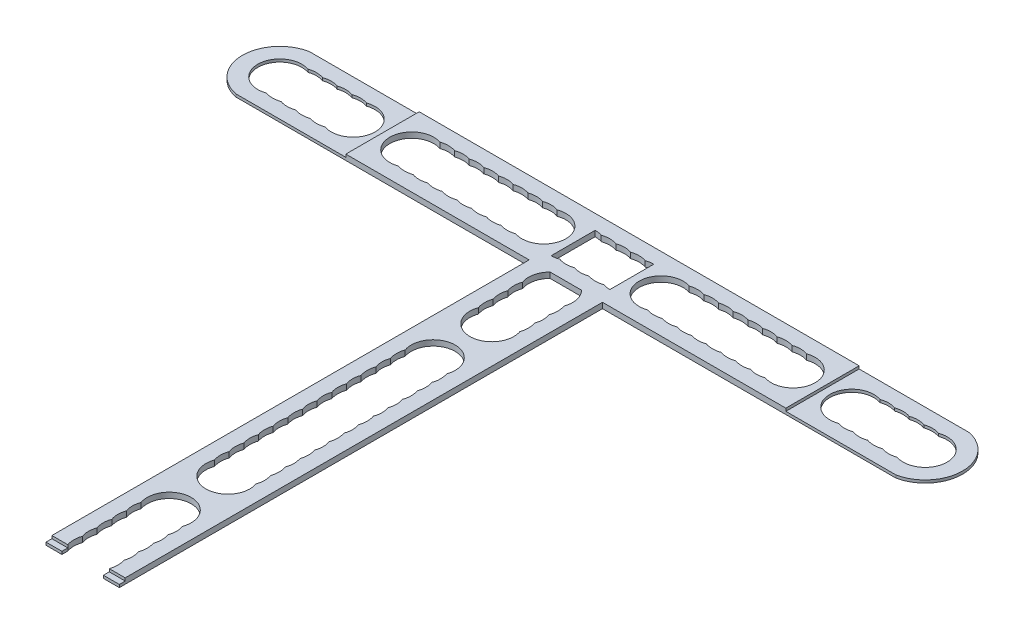
SolidWorks part; units mm, degrees
note: The reader was unsure of these and kept them because the rebuilt part matched: shared geometry of "Sketch3<3>".
ref_plane "Front Plane" through (0, 0, 0) normal (0, 0, 1) x (1, 0, 0)
ref_plane "Top Plane" through (0, 0, 0) normal (0, 1, 0) x (1, 0, 0)
ref_plane "Right Plane" through (0, 0, 0) normal (1, 0, 0) x (0, 0, -1)
sketch "Sketch3" plane through (0, 0, 0) normal (0, 1, 0) x (1, 0, 0)
  line L0 (-112.5, 0) -> (112.5, 0) construction
  line L1 (-112.5, -12.5) -> (112.5, -12.5)
  line L2 (-112.5, -12.5) -> (-112.5, 12.5) construction
  line L3 (-112.5, 12.5) -> (112.5, 12.5)
  line L4 (112.5, -12.5) -> (112.5, 12.5) construction
  line L5 (-112.5, -12.5) -> (112.5, 12.5) construction
  line L6 (-112.5, 12.5) -> (112.5, -12.5) construction
  line L7 (75, 12.5) -> (75, -12.5)
  line L8 (10, 7.5) -> (10, -7.5)
  line L9 (0, 12.5) -> (0, -12.5) construction
  line L10 (0, 12.5) -> (0, -12.5)
  arc A0 (-2.5, 7.0711) -> (2.5, 7.0711) centre (0, 0) cw
  arc A1 (2.5, 7.0711) -> (7.5, 7.0711) centre (5, 0) cw
  arc A2 (7.5, 7.0711) -> (12.5, 7.0711) centre (10, 0) cw
  arc A3 (12.5, 7.0711) -> (17.5, 7.0711) centre (15, 0) cw
  arc A4 (17.5, 7.0711) -> (22.5, 7.0711) centre (20, 0) cw
  arc A5 (22.5, 7.0711) -> (27.5, 7.0711) centre (25, 0) cw
  arc A6 (27.5, 7.0711) -> (32.5, 7.0711) centre (30, 0) cw
  arc A7 (32.5, 7.0711) -> (37.5, 7.0711) centre (35, 0) cw
  arc A8 (37.5, 7.0711) -> (42.5, 7.0711) centre (40, 0) cw
  arc A9 (42.5, 7.0711) -> (47.5, 7.0711) centre (45, 0) cw
  arc A10 (47.5, 7.0711) -> (52.5, 7.0711) centre (50, 0) cw
  arc A11 (52.5, 7.0711) -> (57.5, 7.0711) centre (55, 0) cw
  arc A12 (57.5, 7.0711) -> (62.5, 7.0711) centre (60, 0) cw
  arc A13 (62.5, 7.0711) -> (67.5, 7.0711) centre (65, 0) cw
  arc A14 (67.5, 7.0711) -> (72.5, 7.0711) centre (70, 0) cw
  arc A15 (72.5, 7.0711) -> (77.5, 7.0711) centre (75, 0) cw
  arc A16 (77.5, 7.0711) -> (82.5, 7.0711) centre (80, 0) cw
  arc A17 (82.5, 7.0711) -> (87.5, 7.0711) centre (85, 0) cw
  arc A18 (87.5, 7.0711) -> (92.5, 7.0711) centre (90, 0) cw
  arc A19 (92.5, 7.0711) -> (97.5, 7.0711) centre (95, 0) cw
  arc A20 (97.5, 7.0711) -> (102.5, 7.0711) centre (100, 0) cw
  arc A21 (102.5, 7.0711) -> (107.5, 7.0711) centre (105, 0) cw
  arc A22 (107.5, 7.0711) -> (112.5, 7.0711) centre (110, 0) cw
  arc A23 (107.5, -7.0711) -> (112.5, -7.0711) centre (110, 0) ccw
  arc A24 (102.5, -7.0711) -> (107.5, -7.0711) centre (105, 0) ccw
  arc A25 (97.5, -7.0711) -> (102.5, -7.0711) centre (100, 0) ccw
  arc A26 (92.5, -7.0711) -> (97.5, -7.0711) centre (95, 0) ccw
  arc A27 (87.5, -7.0711) -> (92.5, -7.0711) centre (90, 0) ccw
  arc A28 (82.5, -7.0711) -> (87.5, -7.0711) centre (85, 0) ccw
  arc A29 (77.5, -7.0711) -> (82.5, -7.0711) centre (80, 0) ccw
  arc A30 (72.5, -7.0711) -> (77.5, -7.0711) centre (75, 0) ccw
  arc A31 (67.5, -7.0711) -> (72.5, -7.0711) centre (70, 0) ccw
  arc A32 (62.5, -7.0711) -> (67.5, -7.0711) centre (65, 0) ccw
  arc A33 (57.5, -7.0711) -> (62.5, -7.0711) centre (60, 0) ccw
  arc A34 (52.5, -7.0711) -> (57.5, -7.0711) centre (55, 0) ccw
  arc A35 (47.5, -7.0711) -> (52.5, -7.0711) centre (50, 0) ccw
  arc A36 (42.5, -7.0711) -> (47.5, -7.0711) centre (45, 0) ccw
  arc A37 (37.5, -7.0711) -> (42.5, -7.0711) centre (40, 0) ccw
  arc A38 (32.5, -7.0711) -> (37.5, -7.0711) centre (35, 0) ccw
  arc A39 (27.5, -7.0711) -> (32.5, -7.0711) centre (30, 0) ccw
  arc A40 (22.5, -7.0711) -> (27.5, -7.0711) centre (25, 0) ccw
  arc A41 (17.5, -7.0711) -> (22.5, -7.0711) centre (20, 0) ccw
  arc A42 (12.5, -7.0711) -> (17.5, -7.0711) centre (15, 0) ccw
  arc A43 (7.5, -7.0711) -> (12.5, -7.0711) centre (10, 0) ccw
  arc A44 (2.5, -7.0711) -> (7.5, -7.0711) centre (5, 0) ccw
  arc A45 (-2.5, -7.0711) -> (2.5, -7.0711) centre (0, 0) ccw
  arc A46 (112.5, 7.0711) -> (112.5, -7.0711) centre (110, 0) cw
  arc A47 (112.5, 12.5) -> (112.5, -12.5) centre (110, 0) cw
  arc A48 (67.5, 7.0711) -> (67.5, -7.0711) centre (65, 0) cw
  arc A49 (82.5, 7.0711) -> (82.5, -7.0711) centre (85, 0) ccw
  arc A50 (17.5, 7.0711) -> (17.5412, -7.0855) centre (20, 0) ccw
  point P0 (0, 0)
  point P44 (0, 0)
  point P51 (0, 0)
  dimension "D4" = 7.5
  dimension "D1" = 225
  dimension "D2" = 25
  dimension "D3" = 5
  dimension "D6" = 75
  dimension "D5" = 23
extrude "Boss-Extrude1" add sketch "Sketch3" along normal blind 1.9 contours A47 L3 L10 A0 A1 A2 A3 A4 A5 A6 A7 A8 A9 A10 A11 A12 A13 A14 A15 A16 A17 A18 A19 A20 A21 A22 A46 A23 A24 A25 A26 A27 A28 A29 A30 A31 A32 A33 A34 A35 A36 A37 A38 A39 A40 A41 A42 A43 | A50 A3 A2 L8 A43 A42 | A45 L10 L1 L7 A30 A31 A32 A33 A34 A35 A36 A37 A38 A39 A40 A41 A42 A43 A44 | A14 A48 A31 A30 L7 A15
extrude "Boss-Extrude4" add sketch "Sketch3<3>" along normal blind 0.95 contours A47 L3 L7 A15 A16 A17 A18 A19 A20 A21 A22 A46 A23 A24 A25 A26 A27 A28 A29 A30 L1 | A49 A16 A15 L7 A30 A29
sketch "Sketch3<3>" plane through (0, 0, 0) normal (0, 1, 0) x (1, 0, 0) same geometry as "Sketch3"
mirror "Mirror1" about plane through (0, 0, 0) normal (1, 0, 0) of "Boss-Extrude4", "Boss-Extrude1"
sketch "Sketch4" plane through (0, 0, 0) normal (0, 1, 0) x (1, 0, 0)
  line L0 (-75, -12.5) -> (75, -12.5) construction
  line L1 (-12.5, -382.9289) -> (12.5, -382.9289)
  line L2 (-12.5, -382.9289) -> (-12.5, -12.5)
  line L3 (-12.5, -12.5) -> (12.5, -12.5)
  line L4 (12.5, -382.9289) -> (12.5, -12.5)
  line L5 (-12.5, -382.9289) -> (12.5, -12.5) construction
  line L6 (-12.5, -12.5) -> (12.5, -382.9289) construction
  line L7 (0, 0) -> (0, -382.9289) construction
  line L8 (-12.5, -175.2145) -> (12.5, -175.2145)
  line L9 (-12.5, -46.875) -> (12.5, -46.875) construction
  line L10 (-12.5, -140.625) -> (12.5, -140.625) construction
  arc A0 (7.0711, -195.2145) -> (7.0711, -200.2145) centre (0, -197.7145) cw
  arc A1 (7.0711, -190.2145) -> (7.0711, -195.2145) centre (0, -192.7145) cw
  arc A2 (7.0711, -185.2145) -> (7.0711, -190.2145) centre (0, -187.7145) cw
  arc A3 (7.0711, -180.2145) -> (7.0711, -185.2145) centre (0, -182.7145) cw
  arc A4 (7.0711, -175.2145) -> (7.0711, -180.2145) centre (0, -177.7145) cw
  arc A5 (7.0711, -170.2145) -> (7.0711, -175.2145) centre (0, -172.7145) cw
  arc A6 (7.0711, -165.2145) -> (7.0711, -170.2145) centre (0, -167.7145) cw
  arc A7 (7.0711, -160.2145) -> (7.0711, -165.2145) centre (0, -162.7145) cw
  arc A8 (7.0711, -155.2145) -> (7.0711, -160.2145) centre (0, -157.7145) cw
  arc A9 (7.0711, -150.2145) -> (7.0711, -155.2145) centre (0, -152.7145) cw
  arc A10 (7.0711, -145.2145) -> (7.0711, -150.2145) centre (0, -147.7145) cw
  arc A11 (7.0711, -140.2145) -> (7.0711, -145.2145) centre (0, -142.7145) cw
  arc A12 (7.0711, -135.2145) -> (7.0711, -140.2145) centre (0, -137.7145) cw
  arc A13 (7.0711, -130.2145) -> (7.0711, -135.2145) centre (0, -132.7145) cw
  arc A14 (7.0711, -125.2145) -> (7.0711, -130.2145) centre (0, -127.7145) cw
  arc A15 (7.0711, -120.2145) -> (7.0711, -125.2145) centre (0, -122.7145) cw
  arc A16 (7.0711, -115.2145) -> (7.0711, -120.2145) centre (0, -117.7145) cw
  arc A17 (7.0711, -110.2145) -> (7.0711, -115.2145) centre (0, -112.7145) cw
  arc A18 (7.0711, -105.2145) -> (7.0711, -110.2145) centre (0, -107.7145) cw
  arc A19 (7.0711, -100.2145) -> (7.0711, -105.2145) centre (0, -102.7145) cw
  arc A20 (7.0711, -95.2145) -> (7.0711, -100.2145) centre (0, -97.7145) cw
  arc A21 (7.0711, -90.2145) -> (7.0711, -95.2145) centre (0, -92.7145) cw
  arc A22 (7.0711, -85.2145) -> (7.0711, -90.2145) centre (0, -87.7145) cw
  arc A23 (7.0711, -80.2145) -> (7.0711, -85.2145) centre (0, -82.7145) cw
  arc A24 (7.0711, -75.2145) -> (7.0711, -80.2145) centre (0, -77.7145) cw
  arc A25 (7.0711, -70.2145) -> (7.0711, -75.2145) centre (0, -72.7145) cw
  arc A26 (7.0711, -65.2145) -> (7.0711, -70.2145) centre (0, -67.7145) cw
  arc A27 (7.0711, -60.2145) -> (7.0711, -65.2145) centre (0, -62.7145) cw
  arc A28 (7.0711, -55.2145) -> (7.0711, -60.2145) centre (0, -57.7145) cw
  arc A29 (7.0711, -50.2145) -> (7.0711, -55.2145) centre (0, -52.7145) cw
  arc A30 (7.0711, -45.2145) -> (7.0711, -50.2145) centre (0, -47.7145) cw
  arc A31 (7.0711, -40.2145) -> (7.0711, -45.2145) centre (0, -42.7145) cw
  arc A32 (7.0711, -35.2145) -> (7.0711, -40.2145) centre (0, -37.7145) cw
  arc A33 (7.0711, -30.2145) -> (7.0711, -35.2145) centre (0, -32.7145) cw
  arc A34 (7.0711, -25.2145) -> (7.0711, -30.2145) centre (0, -27.7145) cw
  arc A35 (7.0711, -20.2145) -> (7.0711, -25.2145) centre (0, -22.7145) cw
  arc A36 (7.0711, -15.2145) -> (7.0711, -20.2145) centre (0, -17.7145) cw
  arc A37 (-7.0711, -195.2145) -> (-7.0711, -200.2145) centre (0, -197.7145) ccw
  arc A38 (-7.0711, -190.2145) -> (-7.0711, -195.2145) centre (0, -192.7145) ccw
  arc A39 (-7.0711, -185.2145) -> (-7.0711, -190.2145) centre (0, -187.7145) ccw
  arc A40 (-7.0711, -180.2145) -> (-7.0711, -185.2145) centre (0, -182.7145) ccw
  arc A41 (-7.0711, -175.2145) -> (-7.0711, -180.2145) centre (0, -177.7145) ccw
  arc A42 (-7.0711, -170.2145) -> (-7.0711, -175.2145) centre (0, -172.7145) ccw
  arc A43 (-7.0711, -165.2145) -> (-7.0711, -170.2145) centre (0, -167.7145) ccw
  arc A44 (-7.0711, -160.2145) -> (-7.0711, -165.2145) centre (0, -162.7145) ccw
  arc A45 (-7.0711, -155.2145) -> (-7.0711, -160.2145) centre (0, -157.7145) ccw
  arc A46 (-7.0711, -150.2145) -> (-7.0711, -155.2145) centre (0, -152.7145) ccw
  arc A47 (-7.0711, -145.2145) -> (-7.0711, -150.2145) centre (0, -147.7145) ccw
  arc A48 (-7.0711, -140.2145) -> (-7.0711, -145.2145) centre (0, -142.7145) ccw
  arc A49 (-7.0711, -135.2145) -> (-7.0711, -140.2145) centre (0, -137.7145) ccw
  arc A50 (-7.0711, -130.2145) -> (-7.0711, -135.2145) centre (0, -132.7145) ccw
  arc A51 (-7.0711, -125.2145) -> (-7.0711, -130.2145) centre (0, -127.7145) ccw
  arc A52 (-7.0711, -120.2145) -> (-7.0711, -125.2145) centre (0, -122.7145) ccw
  arc A53 (-7.0711, -115.2145) -> (-7.0711, -120.2145) centre (0, -117.7145) ccw
  arc A54 (-7.0711, -110.2145) -> (-7.0711, -115.2145) centre (0, -112.7145) ccw
  arc A55 (-7.0711, -105.2145) -> (-7.0711, -110.2145) centre (0, -107.7145) ccw
  arc A56 (-7.0711, -100.2145) -> (-7.0711, -105.2145) centre (0, -102.7145) ccw
  arc A57 (-7.0711, -95.2145) -> (-7.0711, -100.2145) centre (0, -97.7145) ccw
  arc A58 (-7.0711, -90.2145) -> (-7.0711, -95.2145) centre (0, -92.7145) ccw
  arc A59 (-7.0711, -85.2145) -> (-7.0711, -90.2145) centre (0, -87.7145) ccw
  arc A60 (-7.0711, -80.2145) -> (-7.0711, -85.2145) centre (0, -82.7145) ccw
  arc A61 (-7.0711, -75.2145) -> (-7.0711, -80.2145) centre (0, -77.7145) ccw
  arc A62 (-7.0711, -70.2145) -> (-7.0711, -75.2145) centre (0, -72.7145) ccw
  arc A63 (-7.0711, -65.2145) -> (-7.0711, -70.2145) centre (0, -67.7145) ccw
  arc A64 (-7.0711, -60.2145) -> (-7.0711, -65.2145) centre (0, -62.7145) ccw
  arc A65 (-7.0711, -55.2145) -> (-7.0711, -60.2145) centre (0, -57.7145) ccw
  arc A66 (-7.0711, -50.2145) -> (-7.0711, -55.2145) centre (0, -52.7145) ccw
  arc A67 (-7.0711, -45.2145) -> (-7.0711, -50.2145) centre (0, -47.7145) ccw
  arc A68 (-7.0711, -40.2145) -> (-7.0711, -45.2145) centre (0, -42.7145) ccw
  arc A69 (-7.0711, -35.2145) -> (-7.0711, -40.2145) centre (0, -37.7145) ccw
  arc A70 (-7.0711, -30.2145) -> (-7.0711, -35.2145) centre (0, -32.7145) ccw
  arc A71 (-7.0711, -25.2145) -> (-7.0711, -30.2145) centre (0, -27.7145) ccw
  arc A72 (-7.0711, -20.2145) -> (-7.0711, -25.2145) centre (0, -22.7145) ccw
  arc A73 (-7.0711, -15.2145) -> (-7.0711, -20.2145) centre (0, -17.7145) ccw
  arc A74 (7.0711, -15.2145) -> (-7.0711, -15.2145) centre (0, -17.7145) ccw
  arc A75 (-7.0711, -40.2145) -> (7.0711, -40.2145) centre (0, -37.7145) ccw
  arc A76 (7.0711, -55.2145) -> (-7.0711, -55.2145) centre (0, -57.7145) ccw
  arc A77 (-7.0711, -130.2145) -> (7.0711, -130.2145) centre (0, -127.7145) ccw
  arc A78 (7.0711, -145.2145) -> (-7.0711, -145.2145) centre (0, -147.7145) ccw
  point P0 (0, -197.7145)
  point P134 (0, 0)
  dimension "D4" = 7.5
  dimension "D3" = 5
  dimension "D1" = 25
  dimension "D2" = 390
  dimension "D6" = 46.875
  dimension "D7" = 93.75
  dimension "D5" = 37
extrude "Boss-Extrude2" add sketch "Sketch4" along normal blind 1.9
sketch "Sketch5" plane through (0, 0, 0) normal (0, 1, 0) x (1, 0, 0)
  line L1 (-12.5, -175.2145) -> (-7.0711, -175.2145)
  line L2 (-12.5, -175.2145) -> (-12.5, -177.2145)
  line L3 (-12.5, -177.2145) -> (-7.0711, -177.2145)
  line L4 (-7.0711, -175.2145) -> (-7.0711, -177.2145)
  line L5 (7.0711, -175.2145) -> (12.5, -175.2145)
  line L6 (7.0711, -175.2145) -> (7.0711, -177.2145)
  line L7 (7.0711, -177.2145) -> (12.5, -177.2145)
  line L8 (12.5, -175.2145) -> (12.5, -177.2145)
  dimension "D1" = 2
extrude "Boss-Extrude3" add sketch "Sketch5" along normal blind 0.95
equation "\"diameter_electrode_outer\"= 15mm"
equation "\"width_wing\"= 5mm"
equation "\"rad_curve\"= \"diameter_electrode_outer\" / 2"
equation "\"length_wing\"= 10mm"
equation "\"range_electrode_move_horizontal\"= ( \"length_wing\" / 2 ) * 66"
equation "\"length_slit_horizontal\"= \"diameter_electrode_outer\" + \"range_electrode_move_horizontal\""
equation "\"width_frame\"= \"diameter_electrode_outer\" + \"width_wing\" * 2"
equation "\"height_frame\"= 1.9mm"
equation "\"diameter_fluid_tank_outer\"= 60mm"
equation "\"width_frame_support\"= 10mm"
equation "\"D1@Fillet2\"=\"rad_curve\""
equation "\"range_electrode_move_vertical\"= ( \"length_wing\" / 2 ) * 75"
equation "\"length_slit_vertical\"= \"diameter_electrode_outer\" + \"range_electrode_move_vertical\""
equation "\"circumference_head\"= 600mm"
equation "\"range_electrode_move_front\"= \"circumference_head\" * 3.5 / 10"
equation "\"length_slit_front\"= \"range_electrode_move_front\" + \"diameter_electrode_outer\""
equation "\"D1@Sketch3\"=\"length_slit_front\""
equation "\"D2@Sketch3\"=\"diameter_electrode_outer\"+2*\"width_wing\""
equation "\"D3@Sketch3\"=\"length_wing\"/2"
equation "\"D4@Sketch3\"=\"rad_curve\""
equation "\"D6@Sketch3\"=\"circumference_head\"/10+\"diameter_electrode_outer\""
equation "\"D1@Boss-Extrude1\"=\"height_frame\""
equation "\"D1@Sketch4\"=\"diameter_electrode_outer\"+2*\"width_wing\""
equation "\"D2@Sketch4\"=\"length_slit_vertical\""
equation "\"D3@Sketch4\"=\"length_wing\"/2"
equation "\"D4@Sketch4\"=\"rad_curve\""
equation "\"D1@Boss-Extrude2\"=\"height_frame\""
equation "\"width_connect\"= 2mm"
equation "\"height_connect\"= \"height_frame\" / 2"
equation "\"D1@Boss-Extrude3\"=\"height_connect\""
equation "\"D1@Sketch5\"=\"width_connect\""
equation "\"D1@Boss-Extrude4\"=\"height_frame\"/2"
equation "\"D6@Sketch4\"=\"range_electrode_move_vertical\"/8"
equation "\"D7@Sketch4\"=\"range_electrode_move_vertical\"/4"
equation "\"length_slit_vertical\"= \"range_electrode_move_vertical\" + \"diameter_electrode_outer\""
